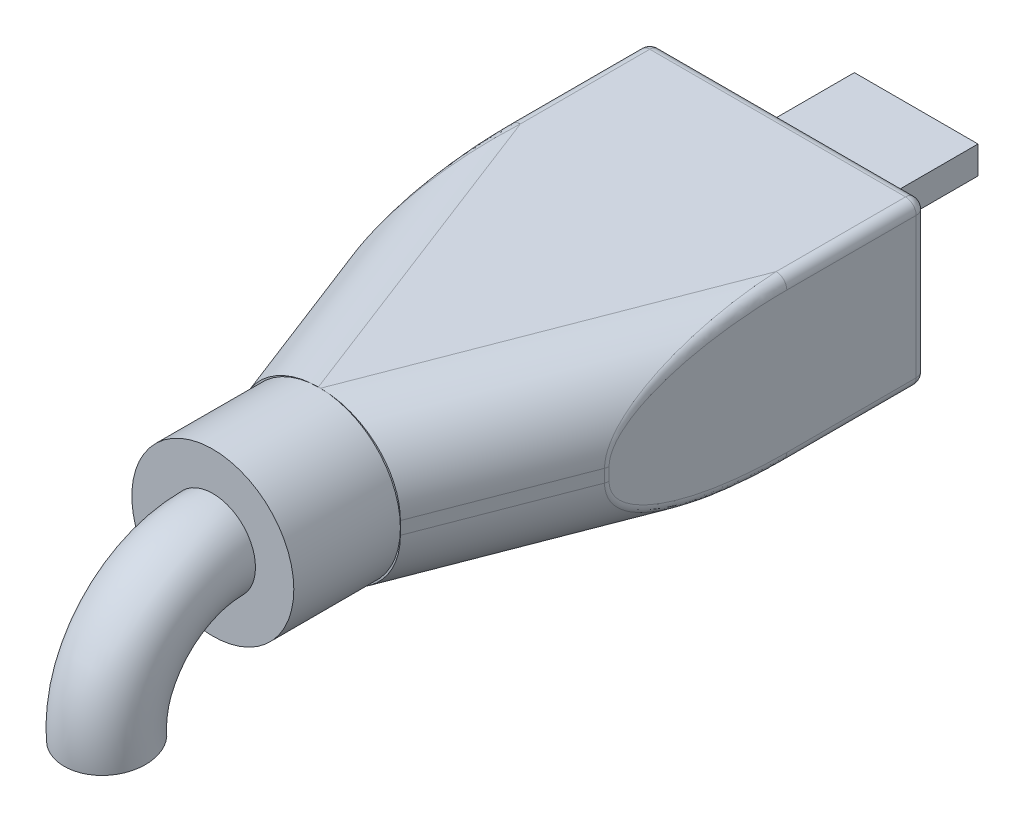
SolidWorks part; units mm, degrees
ref_plane "Front Plane" through (0, 0, 0) normal (0, 0, 1) x (1, 0, 0)
ref_plane "Top Plane" through (0, 0, 0) normal (0, 1, 0) x (1, 0, 0)
ref_plane "Right Plane" through (0, 0, 0) normal (1, 0, 0) x (0, 0, -1)
sketch "Sketch1" plane through (0, 0, 0) normal (0, 0, 1) x (1, 0, 0)
  line L1 (-6.5, -3.8) -> (6.5, -3.8)
  line L2 (-6.5, -3.8) -> (-6.5, 3.8)
  line L3 (-6.5, 3.8) -> (6.5, 3.8)
  line L4 (6.5, -3.8) -> (6.5, 3.8)
  line L5 (-6.5, -3.8) -> (6.5, 3.8) construction
  line L6 (-6.5, 3.8) -> (6.5, -3.8) construction
  point P0 (0, 0)
  dimension "D1" = 7.6
  dimension "D2" = 13
extrude "Boss-Extrude1" add sketch "Sketch1" along normal blind 22
sketch "Sketch2" plane through (0, 0, 0) normal (0, 0, 1) x (1, 0, 0)
  line L1 (-2.9, -1.15) -> (2.9, -1.15)
  line L2 (-2.9, -1.15) -> (-2.9, 1.15)
  line L3 (-2.9, 1.15) -> (2.9, 1.15)
  line L4 (2.9, -1.15) -> (2.9, 1.15)
  line L5 (-2.9, -1.15) -> (2.9, 1.15) construction
  line L6 (-2.9, 1.15) -> (2.9, -1.15) construction
  point P1 (0, 0)
  dimension "D1" = 5.8
  dimension "D2" = 2.3
extrude "Boss-Extrude2" add sketch "Sketch2" against normal blind 6
chamfer "Chamfer1" distance 1 angle 45 2 edges at (-2.9, -1.15, -3) (2.9, -1.15, -3)
sketch "Sketch3" plane through (0, 0, 22) normal (0, 0, 1) x (1, 0, 0)
  line L0 (6.5, 3.8) -> (-6.5, 3.8) construction
  circle A0 centre (0, 0) radius 3.8
extrude "Boss-Extrude3" add sketch "Sketch3" along normal blind 5
sketch "Sketch4" plane through (0, 0, 0) normal (1, 0, 0) x (0, 0, -1)
  line L4 (-27, 3.8) -> (-27, -3.8) construction
  arc A0 (-27, 0) -> (-31.9814, -5.4309) centre (-27, -5) ccw
  dimension "D1" = 5
sweep "Sweep1" add path "Sketch4" circular profile diameter 4 parameters "D3"=4
chamfer "Chamfer2" distance 7 distance2 2.7 2 edges at (-6.5, 0, 22) (6.5, 0, 22) first distance on face at (-6.5, 0, 11) first distance on face at (6.5, 0, 11)
fillet "Fillet1" radius 3.5 4 edges at (-5.15, -3.8, 18.5) (5.15, -3.8, 18.5) (-5.15, 3.8, 18.5) (5.15, 3.8, 18.5)
fillet "Fillet2" radius 0.5 14 edges at (6.5, -3.8, 2.6372) (6.5, -2.7749, 12.1514) (6.5, 0, 15) (6.5, 2.7749, 12.1514) (-6.5, -3.8, 2.6372) (-6.5, -2.7749, 12.1514) (-6.5, 0, 15) (-6.5, 2.7749, 12.1514) (0, -3.8, 0) (-6.5, 0, 0) (0, 3.8, 0) (6.5, 0, 0) (6.5, 3.8, 2.6372) (-6.5, 3.8, 2.6372)
other "Freeze***"
